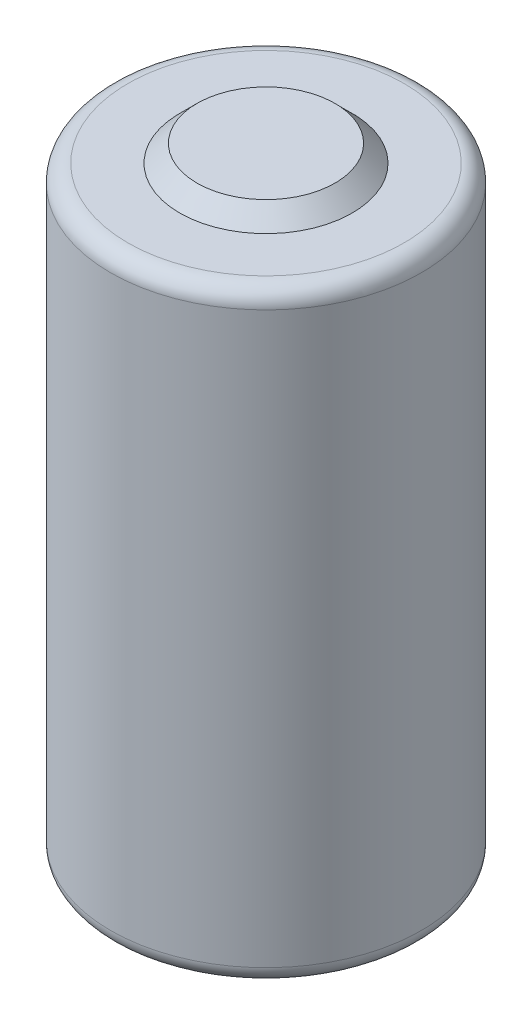
SolidWorks part; units mm, degrees
ref_plane "Front Plane" through (0, 0, 0) normal (0, 0, 1) x (1, 0, 0)
ref_plane "Top Plane" through (0, 0, 0) normal (0, 1, 0) x (1, 0, 0)
ref_plane "Right Plane" through (0, 0, 0) normal (1, 0, 0) x (0, 0, -1)
sketch "Sketch1" plane through (0, 0, 0) normal (0, 1, 0) x (1, 0, 0)
  circle A0 centre (0, 0) radius 9
  dimension "D1" = 18
extrude "Boss-Extrude1" add sketch "Sketch1" along normal blind 35
sketch "Sketch2" plane through (0, 35, 0) normal (0, 1, 0) x (1, 0, 0)
  circle A0 centre (0, 0) radius 4
  dimension "D1" = 8
extrude "Boss-Extrude2" add sketch "Sketch2" along normal blind 1
fillet "Fillet1" radius 1 2 edges at (0, 0, 9) (0, 35, 9)
chamfer "Chamfer1" distance 1 angle 45 1 edges at (0, 35, 4)
